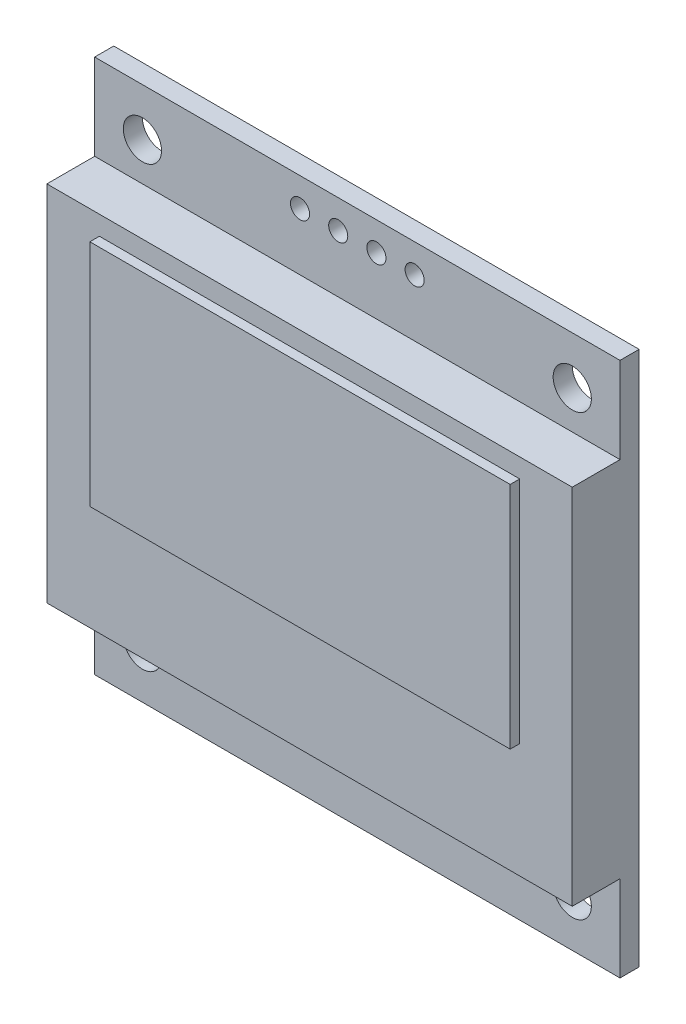
SolidWorks part; units mm, degrees
ref_plane "Front Plane" through (0, 0, 0) normal (0, 0, 1) x (1, 0, 0)
ref_plane "Top Plane" through (0, 0, 0) normal (0, 1, 0) x (1, 0, 0)
ref_plane "Right Plane" through (0, 0, 0) normal (1, 0, 0) x (0, 0, -1)
sketch "Sketch1" plane through (0, 0, 0) normal (0, 0, 1) x (1, 0, 0)
  line L0 (13.75, 3.4478) -> (13.75, -24.5522) construction
  line L1 (0, 3.4478) -> (27.5, 3.4478)
  line L2 (0, 3.4478) -> (0, -24.5522)
  line L3 (0, -24.5522) -> (27.5, -24.5522)
  line L4 (27.5, 3.4478) -> (27.5, -24.5522)
  line L5 (0, -20.0522) -> (27.5, -20.0522)
  line L6 (0, -20.0522) -> (0, -1.0522)
  line L7 (0, -1.0522) -> (27.5, -1.0522)
  line L8 (27.5, -20.0522) -> (27.5, -1.0522)
  line L9 (0, -10.5522) -> (27.5, -10.5522) construction
  line L11 (2.75, -2.0522) -> (24.75, -2.0522)
  line L12 (2.75, -2.0522) -> (2.75, -14.0522)
  line L13 (2.75, -14.0522) -> (24.75, -14.0522)
  line L14 (24.75, -2.0522) -> (24.75, -14.0522)
  circle A0 centre (14.75, 1.9478) radius 0.5
  circle A1 centre (16.75, 1.9478) radius 0.5
  circle A2 centre (10.75, 1.9478) radius 0.5
  circle A3 centre (12.75, 1.9478) radius 0.5
  circle A4 centre (25, 0.9478) radius 1
  circle A5 centre (25, -22.0522) radius 1
  circle A6 centre (2.5, -22.0522) radius 1
  circle A7 centre (2.5, 0.9478) radius 1
  dimension "D5" = 1
  dimension "D10" = 2
  dimension "D12" = 2.5
  dimension "D1" = 27.5
  dimension "D2" = 28
  dimension "D3" = 4.5
  dimension "D4" = 4.5
  dimension "D6" = 1.5
  dimension "D7" = 1
  dimension "D8" = 2
  dimension "D9" = 1.5
  dimension "D11" = 2.5
  dimension "D13" = 12
  dimension "D14" = 22
  dimension "D15" = 2.75
  dimension "D16" = 1
extrude "Boss-Extrude1" add sketch "Sketch1" along normal blind 3.5 contours L7 L2 L5 L4 region at (13.75, -1.3865, 0)
extrude "Boss-Extrude2" add sketch "Sketch1<3>" along normal blind 1 contours L2 L7 L4 L1 A3 A0 A1 A2 A4 A7 | L5 L2 L3 L4 A6 A5 region at (13.75, 1.1909, 0) region at (13.75, -22.3156, 0)
sketch "Sketch1<3>" plane through (0, 0, 0) normal (0, 0, 1) x (1, 0, 0) same geometry as "Sketch1"
extrude "Boss-Extrude3" add sketch "Sketch1<4>" along normal blind 4 contours L14 L11 L12 L13 region at (13.75, -8.0522, 0)
sketch "Sketch1<4>" plane through (0, 0, 0) normal (0, 0, 1) x (1, 0, 0) same geometry as "Sketch1"
